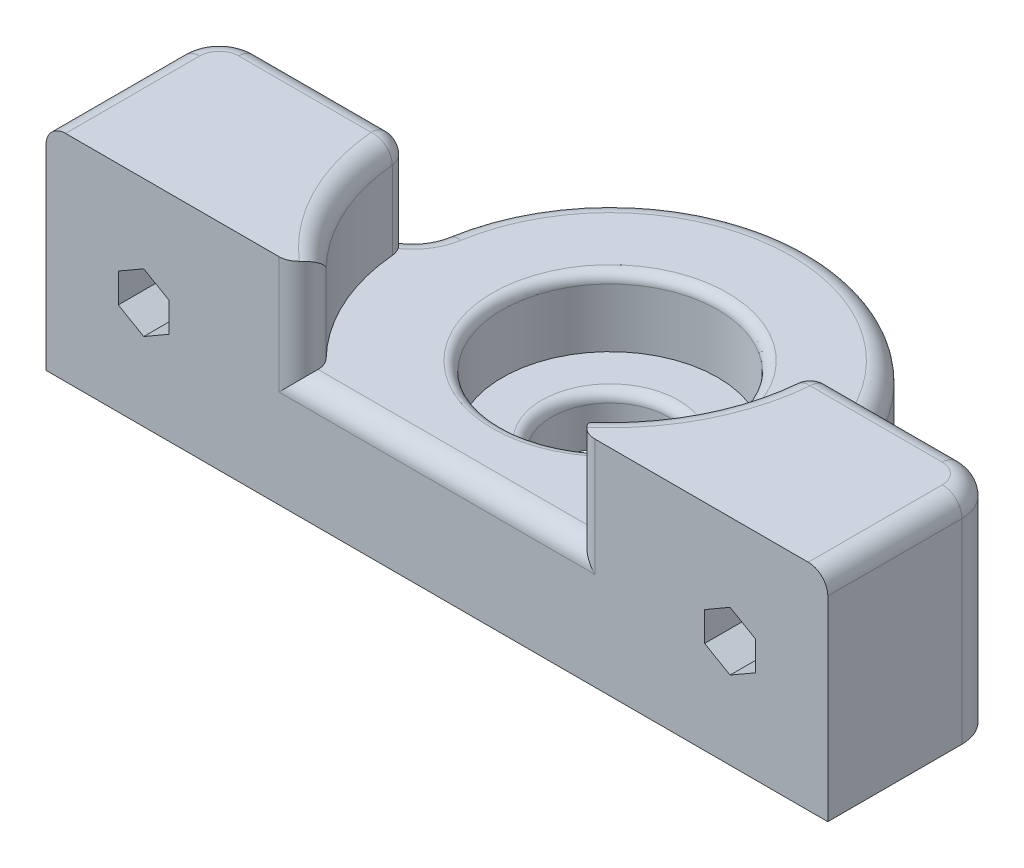
SolidWorks part; units mm, degrees
material "ABS"
ref_plane "Front Plane" through (0, 0, 0) normal (0, 0, 1) x (1, 0, 0)
ref_plane "Top Plane" through (0, 0, 0) normal (0, 1, 0) x (1, 0, 0)
ref_plane "Right Plane" through (0, 0, 0) normal (1, 0, 0) x (0, 0, -1)
sketch "Sketch1" plane through (0, 0, 0) normal (0, 1, 0) x (1, 0, 0)
  line L0 (-40, -17.7241) -> (40, -17.7241)
  line L1 (-40, -17.7241) -> (-40, 0)
  line L2 (-40, 0) -> (-20.55, 0)
  line L3 (40, -17.7241) -> (40, 0)
  line L4 (40, 0) -> (20.55, 0)
  circle A0 centre (0, 0) radius 11.025
  arc A1 (20.55, 0) -> (-20.55, 0) centre (0, 0) ccw
  point P6 (0, -17.7241)
  dimension "D1" = 22.05
  dimension "D2" = 9.525
  dimension "D3" = 17.7241
  dimension "D4" = 80
extrude "Boss-Extrude1" add sketch "Sketch1" along normal blind 12
sketch "Sketch3" plane through (0, 0, 0) normal (0, -1, 0) x (1, 0, 0)
  circle A0 centre (0, 0) radius 11.025
  circle A1 centre (0, 0) radius 6
  dimension "D1" = 22.05
  dimension "D2" = 12
extrude "Boss-Extrude2" add sketch "Sketch3" against normal blind 5
sketch "Sketch4" plane through (0, 12, 0) normal (0, 1, 0) x (1, 0, 0)
  line L0 (-20.55, 0) -> (-40, 0)
  line L1 (-40, 0) -> (-40, -17.7241)
  line L2 (-40, -17.7241) -> (-10.3999, -17.7241)
  line L3 (40, -17.7241) -> (40, 0)
  line L4 (40, 0) -> (20.55, 0)
  line L5 (40, 0) -> (20.55, 0) construction
  line L6 (10.3999, -17.7241) -> (40, -17.7241)
  arc A0 (20.55, 0) -> (-20.55, 0) centre (0, 0) ccw construction
  arc A1 (10.3999, -17.7241) -> (20.55, 0) centre (0, 0) ccw
  arc A2 (-20.55, 0) -> (-10.3999, -17.7241) centre (0, 0) ccw
extrude "Boss-Extrude3" add sketch "Sketch4" along normal blind 10
fillet "Fillet9" radius 4 4 edges at (40, 11, 0) (20.55, 6, 0) (-40, 11, 0) (-20.55, 6, 0)
fillet "Fillet6" radius 2 12 edges at (20.55, 17, 0) (40, 22, 10.8621) (28.275, 22, 0) (17.8328, 22, 10.2124) (-20.55, 17, 0) (-40, 22, 10.8621) (-28.275, 22, 0) (-17.8328, 22, 10.2124) (10.3999, 17, 17.7241) (38.8284, 22, 1.1716) (-38.8284, 22, 1.1716)
fillet "Fillet7" radius 2 4 edges at (0, 12, -20.55) (21.6342, 12, -0.9498) (-21.6342, 12, -0.9498)
fillet "Fillet10" radius 1 2 edges at (0, 5, -6) (0, 12, 11.025)
sketch "Sketch5" plane through (0, 0, 17.7241) normal (0, 0, 1) x (1, 0, 0)
  line L0 (0, 0) -> (0, 22) construction
  line L1 (-40, 0) -> (40, 0) construction
  line L3 (32.6, 12.5011) -> (30, 14.0022)
  line L4 (30, 14.0022) -> (27.4, 12.5011)
  line L5 (27.4, 12.5011) -> (27.4, 9.4989)
  line L6 (27.4, 9.4989) -> (30, 7.9978)
  line L7 (30, 7.9978) -> (32.6, 9.4989)
  line L8 (32.6, 9.4989) -> (32.6, 12.5011)
  line L9 (-27.4, 12.5011) -> (-30, 14.0022)
  line L10 (-30, 14.0022) -> (-32.6, 12.5011)
  line L11 (-32.6, 12.5011) -> (-32.6, 9.4989)
  line L12 (-32.6, 9.4989) -> (-30, 7.9978)
  line L13 (-30, 7.9978) -> (-27.4, 9.4989)
  line L14 (-27.4, 9.4989) -> (-27.4, 12.5011)
  circle A2 centre (30, 11) radius 2.6 construction
  circle A3 centre (-30, 11) radius 2.6 construction
  dimension "D1" = 5.2
  dimension "D2" = 11
  dimension "D3" = 60
  dimension "D4" = 30
  dimension "D6" = 22
extrude "Cut-Extrude1" cut sketch "Sketch5" against normal up to next
sketch "Sketch6" plane through (0, 0, 17.7241) normal (0, 0, 1) x (1, 0, 0)
  point P0 (-30, 11)
  point P1 (30, 11)
ref_axis "Axis1" through (-30, 11, -4.6541) along (0, 0, 1)
ref_axis "Axis2" through (30, 11, -5.1598) along (0, 0, 1)
